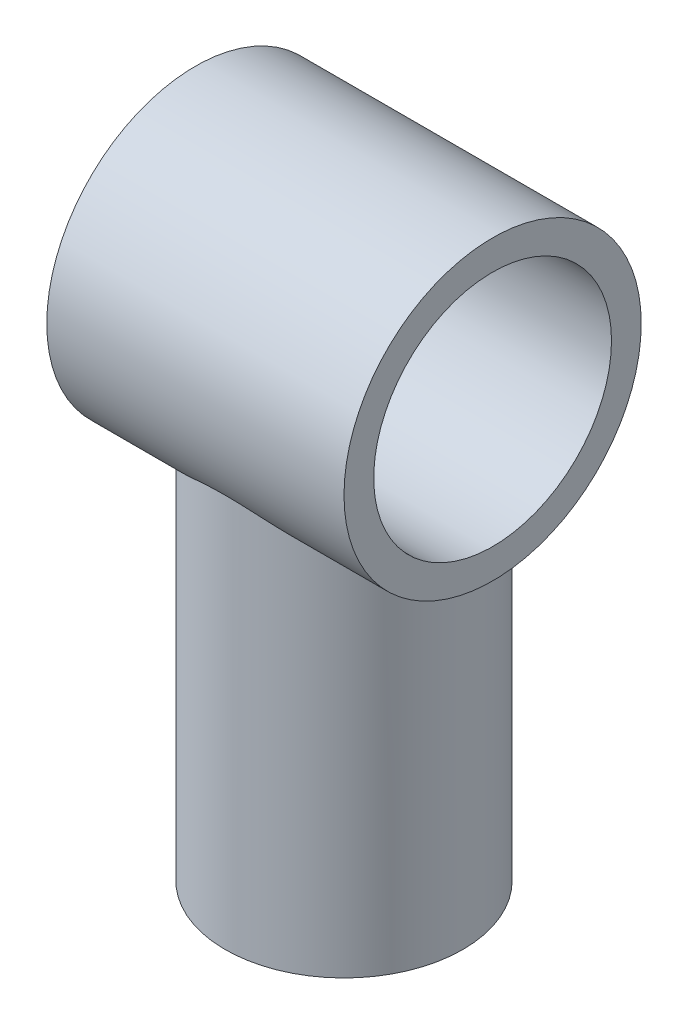
SolidWorks part; units mm, degrees
ref_plane "前视基准面" through (0, 0, 0) normal (0, 0, 1) x (1, 0, 0)
ref_plane "上视基准面" through (0, 0, 0) normal (0, 1, 0) x (1, 0, 0)
ref_plane "右视基准面" through (0, 0, 0) normal (1, 0, 0) x (0, 0, -1)
sketch "草图1" plane through (0, 0, 0) normal (1, 0, 0) x (0, 0, -1)
  circle A0 centre (0, 0) radius 50
extrude "凸台-拉伸1" add sketch "草图1" against normal blind 50 and the other way blind 50
sketch "草图2" plane through (0, 0, 0) normal (1, 0, 0) x (0, 0, -1)
  circle A0 centre (0, 0) radius 40
extrude "切除-拉伸2" cut sketch "草图2" along normal blind 50 and the other way blind 50
ref_plane "基准面1" through (0, -162.4, 0) normal (0, -1, 0) x (-1, 0, 0)
sketch "草图3" plane through (0, -162.4, 0) normal (0, -1, 0) x (-1, 0, 0)
  circle A0 centre (0, 0) radius 40
extrude "凸台-拉伸2" add sketch "草图3" against normal up to surface (112.4 mm away) contours A0 up to face at (50, 0, -50)
